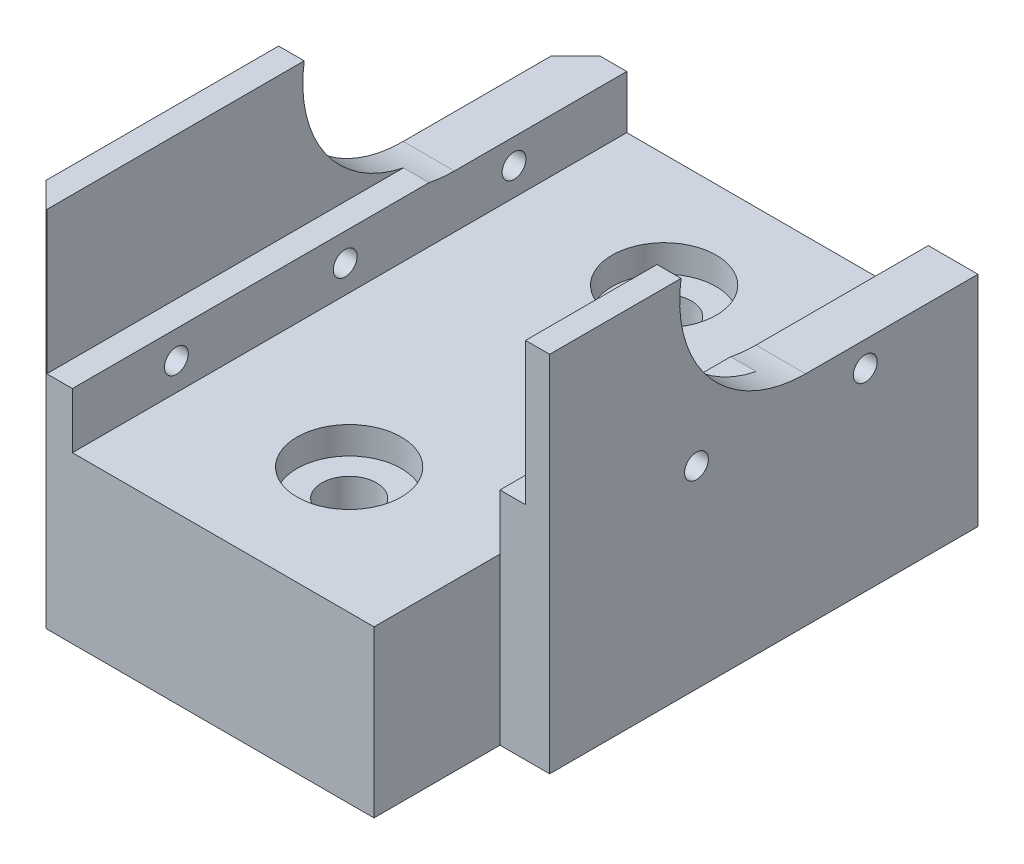
SolidWorks part; units mm, degrees
material "PLA"
ref_plane "Front Plane" through (0, 0, 0) normal (0, 0, 1) x (1, 0, 0)
ref_plane "Top Plane" through (0, 0, 0) normal (0, 1, 0) x (1, 0, 0)
ref_plane "Right Plane" through (0, 0, 0) normal (1, 0, 0) x (0, 0, -1)
sketch "Sketch1" plane through (0, 0, 0) normal (0, 1, 0) x (1, 0, 0)
  line L0 (-22.86, 30.48) -> (22.86, 30.48)
  line L6 (-22.86, 30.48) -> (-22.86, -30.48)
  line L8 (22.86, 30.48) -> (22.86, -30.48)
  line L9 (-22.86, -30.48) -> (22.86, -30.48)
  point P1 (-22.86, 0)
  point P7 (22.86, 0)
  dimension "D3" = 30.48
  dimension "D2" = 45.72
  dimension "D1" = 60.96
  dimension "D4" = 22.86
extrude "Boss-Extrude1" add sketch "Sketch1" along normal blind 6.35
sketch "Sketch2" plane through (0, 6.35, 0) normal (0, 1, 0) x (1, 0, 0)
  line L9 (-22.86, -30.48) -> (22.86, -30.48) construction
  line L10 (-22.86, 30.48) -> (-15.2, 30.48)
  line L11 (-22.86, 30.48) -> (-22.86, -30.48)
  line L12 (-22.86, -30.48) -> (-15.2, -30.48)
  line L13 (-15.2, 30.48) -> (-15.2, -30.48)
  line L14 (22.86, 30.48) -> (-22.86, 30.48) construction
  line L15 (15.2, 30.48) -> (22.86, 30.48)
  line L16 (15.2, 30.48) -> (15.2, -30.48)
  line L17 (15.2, -30.48) -> (22.86, -30.48)
  line L18 (22.86, 30.48) -> (22.86, -30.48)
  dimension "D1" = 7.66
  dimension "D2" = 7.66
extrude "Boss-Extrude2" add sketch "Sketch2" along normal blind 20.955
hole_wizard "M2 Clearance Hole2" positions "Sketch6" profile "Sketch7" hole size "M2" standard "ANSI Metric"
sketch "Sketch6" plane through (22.86, 0, 0) normal (1, 0, 0) x (0, 0, -1)
  line L0 (-30.48, 27.305) -> (-30.48, 0) construction
  line L1 (-30.48, 0) -> (30.48, 0) construction
  point P0 (-14.9172, 10.16)
  dimension "D1" = 15.5628
  dimension "D2" = 10.16
sketch "Sketch7" plane through (22.86, 10.16, 14.9172) normal (0, 1, 0) x (0, 0, -1)
  line L0 (0, 0) -> (0, 46.441)
  line L1 (0, 46.441) -> (1.2, 45.72)
  line L2 (1.2, 45.72) -> (1.2, 0)
  line L5 (1.2, 0) -> (0, 0)
  line L10 (0, 46.441) -> (-1.2, 45.72) construction
  line L11 (0, -6.35) -> (0, 107.95) construction
  dimension "Hole Dia." = 2.4
  dimension "Hole Depth" = 45.72
  dimension "Drill Angle" = 118
pattern_linear "LPattern1" count 3 spacing 17.018 along (0, 0, -1) of "M2 Clearance Hole2"
extrude "Boss-Extrude3" add sketch "Sketch1<3>" against normal blind 2.54
sketch "Sketch1<3>" plane through (0, 0, 0) normal (0, 1, 0) x (1, 0, 0) same geometry as "Sketch1"
sketch "Sketch8" plane through (-22.86, 0, 0) normal (-1, 0, 0) x (0, 0, 1)
  line L0 (-30.48, 27.305) -> (-30.48, -2.54) construction
  line L1 (-30.48, -2.54) -> (-14.605, -2.54)
  line L2 (-30.48, -2.54) -> (-30.48, 3.81)
  line L3 (-30.48, 3.81) -> (-14.605, 3.81)
  line L4 (-14.605, -2.54) -> (-14.605, 3.81)
  line L5 (-30.48, -2.54) -> (30.48, -2.54) construction
  dimension "D1" = 15.875
  dimension "D2" = 6.35
sketch "Sketch11" plane through (15.2, 0, 0) normal (-1, 0, 0) x (0, 0, 1)
  line L0 (30.48, 27.305) -> (30.48, 6.35) construction
  line L1 (-30.48, 27.305) -> (30.48, 27.305)
  line L2 (-30.48, 27.305) -> (-30.48, 12.96)
  line L3 (-30.48, 12.96) -> (30.48, 12.96)
  line L4 (30.48, 27.305) -> (30.48, 12.96)
  dimension "D1" = 14.345
extrude "Cut-Extrude1" cut sketch "Sketch11" against normal mid plane 35.56 from surface starting at plane "Right Plane"
sketch "Sketch12" plane through (22.86, 0, 0) normal (1, 0, 0) x (0, 0, -1)
  line L0 (30.48, 27.305) -> (30.48, -2.54) construction
  line L1 (13.105, 12.7) -> (30.48, 12.7)
  line L2 (30.48, 12.7) -> (30.48, 27.305)
  line L3 (30.48, 27.305) -> (25.6613, 27.305)
  line L5 (-30.48, 27.305) -> (30.48, 27.305) construction
  arc A0 (25.6613, 27.305) -> (13.105, 12.7) centre (13.105, 25.4) ccw
  dimension "D3" = 25.4
  dimension "D1" = 17.375
  dimension "D2" = 1.905
extrude "Cut-Extrude2" cut sketch "Sketch12" against normal through all
fillet "Fillet3" [suppressed] radius 0.762
sketch "Sketch17" plane through (0, -2.54, 0) normal (0, -1, 0) x (1, 0, 0)
  line L0 (-22.86, 30.48) -> (22.86, 30.48) construction
  line L1 (-22.86, 30.48) -> (22.86, 30.48)
  line L2 (-22.86, 30.48) -> (-22.86, -30.48)
  line L3 (-22.86, -30.48) -> (22.86, -30.48)
  line L4 (22.86, 30.48) -> (22.86, -30.48)
  line L5 (22.86, -30.48) -> (-22.86, -30.48) construction
  line L6 (22.86, 30.48) -> (22.86, -30.48) construction
  line L7 (-22.86, -30.48) -> (-22.86, 30.48) construction
extrude "Boss-Extrude4" add sketch "Sketch17" along normal blind 6.785
fillet "Fillet5" [suppressed] radius 0.762
sketch "Sketch19" plane through (0, 6.35, 0) normal (0, 1, 0) x (1, 0, 0)
  line L0 (15.2, 30.48) -> (15.2, -30.48) construction
  line L1 (-15.2, -30.48) -> (15.2, -30.48)
  line L2 (-15.2, -30.48) -> (-15.2, 30.48)
  line L3 (-15.2, 30.48) -> (15.2, 30.48)
  line L4 (15.2, -30.48) -> (15.2, 30.48)
  line L5 (15.2, 30.48) -> (-15.2, 30.48) construction
extrude "Boss-Extrude5" add sketch "Sketch19" along normal blind 1.01
hole_wizard "CBORE for M5 SBHCS2" positions "Sketch20" profile "Sketch21" counterbore size "M5" standard "ANSI Metric" end condition through all
sketch "Sketch20" plane through (0, 7.36, 0) normal (0, 1, 0) x (1, 0, 0)
  point P2 (0, -12.7)
  point P5 (0, 19.05)
  dimension "D1" = 31.75
  dimension "D2" = 12.7
sketch "Sketch21" plane through (0, 7.36, 12.7) normal (1, 0, 0) x (0, 0, 1)
  line L0 (0, 0) -> (0, 16.685)
  line L1 (0, 16.685) -> (2.75, 16.685)
  line L3 (2.75, 16.685) -> (2.75, 2.75)
  line L4 (2.75, 2.75) -> (5.25, 2.75)
  line L5 (5.25, 2.75) -> (5.25, 0)
  line L7 (5.25, 0) -> (0, 0)
  line L11 (0, -6.35) -> (0, 107.95) construction
  dimension "Thru Hole Dia." = 5.5
  dimension "Thru Hole Depth" = 16.685
  dimension "C'Bore Dia." = 10.5
  dimension "C'Bore Depth" = 2.75
fillet "Fillet6" [suppressed] radius 0.762
sketch "Sketch24" plane through (31.5712, -12.7, -14.6188) normal (0, 1, 0) x (0, 0, -1)
  line L0 (-45.0988, 8.7112) -> (-14.0701, 8.7112) construction
  line L1 (-45.0988, 54.4312) -> (-40.0188, 54.4312)
  line L2 (-45.0988, 54.4312) -> (-45.0988, 8.7112)
  line L3 (-45.0988, 8.7112) -> (-40.0188, 8.7112)
  line L4 (-40.0188, 54.4312) -> (-40.0188, 8.7112)
  dimension "D1" = 5.08
extrude "Cut-Extrude3" cut sketch "Sketch24" against normal through all both and the other way through all
sketch "Sketch25" plane through (0, 0, 25.4) normal (0, 0, 1) x (1, 0, 0)
  line L0 (15.2, -9.325) -> (15.2, 27.305)
  line L1 (22.86, -9.325) -> (-22.86, -9.325) construction
  line L3 (22.86, 27.305) -> (22.86, -9.325) construction
  line L4 (15.2, -9.325) -> (22.86, -9.325)
  line L5 (22.86, -9.325) -> (22.86, 27.305)
  line L6 (22.86, 27.305) -> (17.78, 27.305) construction
  line L7 (15.2, 27.305) -> (22.86, 27.305)
  line L8 (15.2, 12.96) -> (15.2, 7.36) construction
extrude "Cut-Extrude4" cut sketch "Sketch25" against normal blind 12.7
sketch "Sketch26" plane through (0, 0, 25.4) normal (0, 0, 1) x (1, 0, 0)
  line L0 (22.86, 27.305) -> (17.78, 27.305) construction
  line L1 (20.46, 27.305) -> (22.86, 27.305)
  line L2 (20.46, 27.305) -> (20.46, -9.325)
  line L3 (20.46, -9.325) -> (22.86, -9.325)
  line L4 (22.86, 27.305) -> (22.86, -9.325)
  line L5 (20.46, 27.305) -> (22.86, -9.325) construction
  line L6 (20.46, -9.325) -> (22.86, 27.305) construction
  line L8 (15.2, -9.325) -> (22.86, -9.325) construction
  line L9 (22.86, -9.325) -> (22.86, 27.305) construction
  point P0 (21.66, 8.99)
  dimension "D1" = 2.4
extrude "Cut-Extrude5" cut sketch "Sketch26" against normal through all
sketch "Sketch27" plane through (0, 0, 25.4) normal (0, 0, 1) x (1, 0, 0)
  line L0 (-17.78, 27.305) -> (-22.86, 27.305) construction
  line L1 (-22.86, 27.305) -> (-20.36, 27.305)
  line L2 (-22.86, 27.305) -> (-22.86, -9.325)
  line L3 (-22.86, -9.325) -> (-20.36, -9.325)
  line L4 (-20.36, 27.305) -> (-20.36, -9.325)
  line L5 (-22.86, 27.305) -> (-20.36, -9.325) construction
  line L6 (-22.86, -9.325) -> (-20.36, 27.305) construction
  line L7 (15.2, -9.325) -> (-22.86, -9.325) construction
  line L8 (-22.86, 27.305) -> (-22.86, -9.325) construction
  point P0 (-21.61, 8.99)
  dimension "D1" = 2.5
extrude "Cut-Extrude6" cut sketch "Sketch27" against normal through all
chamfer "Chamfer1" distance 2.5 angle 45 2 edges at (-20.36, 8.99, 25.4) (-20.36, 1.6875, -30.48)
sketch "Sketch28" plane through (0, 0, -30.48) normal (0, 0, -1) x (-1, 0, 0)
  line L0 (-17.78, 27.305) -> (-20.46, 27.305) construction
  line L1 (-20.46, -9.325) -> (-20.206, -9.325)
  line L2 (-20.46, -9.325) -> (-20.46, 27.305)
  line L3 (-20.46, 27.305) -> (-20.206, 27.305)
  line L4 (-20.206, -9.325) -> (-20.206, 27.305)
  dimension "D1" = 0.254
extrude "Cut-Extrude7" cut sketch "Sketch28" against normal through all
